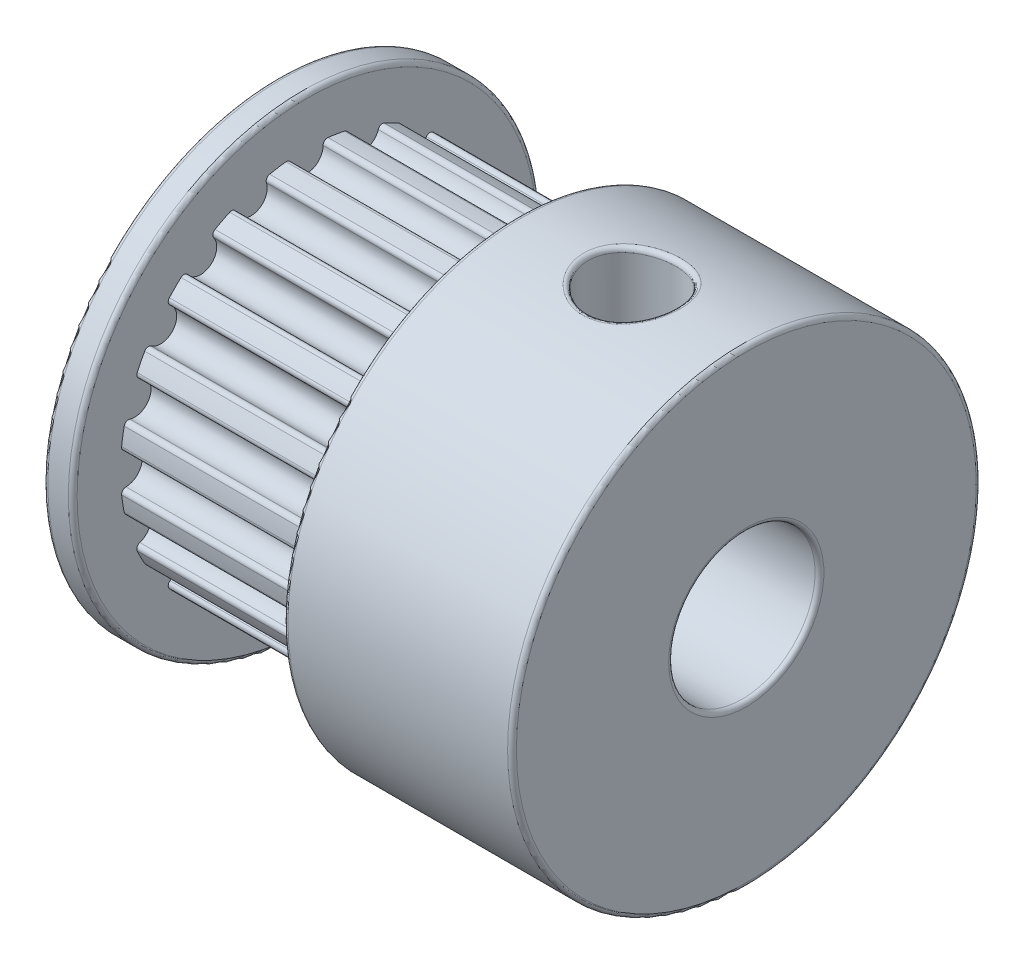
SolidWorks part; units mm, degrees
other "Camera1"
ref_plane "Front Plane" through (0, 0, 0) normal (0, 0, 1) x (1, 0, 0)
ref_plane "Top Plane" through (0, 0, 0) normal (0, 1, 0) x (1, 0, 0)
ref_plane "Right Plane" through (0, 0, 0) normal (1, 0, 0) x (0, 0, -1)
sketch "Sketch1" plane through (0, 0, 0) normal (0, 0, 1) x (1, 0, 0)
  line L1 (0, 0) -> (26.8238, 0) construction
  line L2 (0, 8) -> (1, 8)
  line L4 (0, 8) -> (0, 2.5)
  line L5 (0, 2.5) -> (16, 2.5)
  line L6 (1, 6.37) -> (8.2, 6.37)
  line L7 (8.2, 6.37) -> (8.2, 8)
  line L8 (8.2, 8) -> (16, 8)
  line L9 (16, 8) -> (16, 2.5)
  line L10 (1, 8) -> (1, 6.37)
  dimension "D1" = 8
  dimension "D2" = 1
  dimension "D3" = 5.5
  dimension "D4" = 2.5
  dimension "D5" = 7.2
  dimension "D6" = 7.8
  dimension "D7" = 16
revolve "Revolve1" add sketch "Sketch1" angle 360 about L1
sketch "Sketch2" plane through (8.2, 0, 0) normal (-1, 0, 0) x (0, 0, 1)
  line L0 (0, 6.37) -> (0, 6.18)
  arc A0 (0.5236, 6.3484) -> (-0.5236, 6.3484) centre (0, 0) ccw
  arc A1 (-0.5236, 6.3484) -> (0.5236, 6.3484) centre (0, 6.18) ccw
  dimension "D2" = 1.1
  dimension "D1" = 0.19
extrude "Cut-Extrude1" cut sketch "Sketch2" along normal blind 7.2 contours A1 A0
fillet "Fillet1" radius 0.15 2 edges at (4.6, 6.3484, 0.5236) (4.6, 6.3484, -0.5236)
pattern_circular "CirPattern1" count 20 over 360 about axis through (0, 0, 0) along (-1, 0, 0) of "Fillet1", "Cut-Extrude1"
fillet "Fillet2" radius 0.15 5 edges at (0, 0, 2.5) (16, 0, 8) (8.2, 0, 8) (1, 0, 8) (0, 0, 8)
ref_plane "Plane1" through (0, 8, 0) normal (0, 1, 0) x (1, 0, 0)
sketch "Sketch3" plane through (0, 8, 0) normal (0, 1, 0) x (1, 0, 0)
  circle A0 centre (12.1, 0) radius 1.5
  point P5 (12.1, 0)
  point P9 (12.1, 0.9955)
  dimension "D1" = 3
extrude "Cut-Extrude2" cut sketch "Sketch3" against normal blind 7.2
fillet "Fillet3" radius 0.15 1 edges at (12.4158, 7.8645, -1.4664)
fillet "Fillet4" radius 0.15 1 edges at (16, 0, 2.5)
